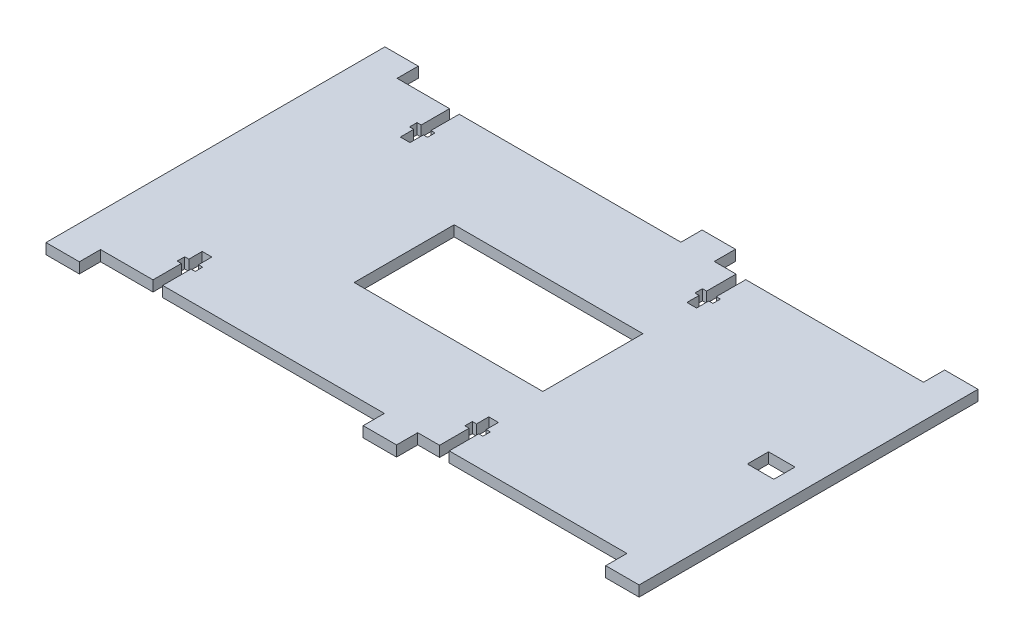
SolidWorks part; units mm, degrees
ref_plane "Front Plane" through (0, 0, 0) normal (0, 0, 1) x (1, 0, 0)
ref_plane "Top Plane" through (0, 0, 0) normal (0, 1, 0) x (1, 0, 0)
ref_plane "Right Plane" through (0, 0, 0) normal (1, 0, 0) x (0, 0, -1)
sketch "Sketch1" plane through (0, 0, 0) normal (0, 1, 0) x (1, 0, 0)
  line L0 (-67.1586, 70.4843) -> (-67.1586, 74.4928)
  line L1 (-92.8881, 91.5843) -> (-82.8881, 91.5843)
  line L2 (-92.8881, 91.5843) -> (-92.8881, -10.0157)
  line L3 (84.9141, 91.5843) -> (84.9141, -10.0157)
  line L5 (-64.2586, 85.2343) -> (2.2019, 85.2343)
  line L6 (-67.1586, 85.2343) -> (-67.1586, 76.7428)
  line L7 (-67.1586, 70.4843) -> (-64.2586, 70.4843)
  line L8 (-64.2586, 85.2343) -> (-64.2586, 76.7428)
  line L9 (-68.4086, 76.7428) -> (-67.1586, 76.7428)
  line L10 (-68.4086, 76.7428) -> (-68.4086, 74.4928)
  line L11 (-68.4086, 74.4928) -> (-67.1586, 74.4928)
  line L12 (-63.0086, 76.7428) -> (-63.0086, 74.4928)
  line L13 (18.7441, 70.4843) -> (18.7441, 74.1476)
  line L14 (-82.8881, 91.5843) -> (-82.8881, 85.2343)
  line L15 (-82.8881, 85.2343) -> (-67.1586, 85.2343)
  line L16 (2.2019, 91.5843) -> (2.2019, 85.2343)
  line L17 (-64.2586, 70.4843) -> (-64.2586, 74.4928)
  line L18 (-64.2586, 74.4928) -> (-63.0086, 74.4928)
  line L19 (-64.2586, 76.7428) -> (-63.0086, 76.7428)
  line L20 (2.2019, 91.5843) -> (12.2019, 91.5843)
  line L21 (21.6441, 85.2343) -> (74.9141, 85.2343)
  line L22 (18.7441, 85.2343) -> (18.7441, 76.3976)
  line L23 (18.7441, 70.4843) -> (21.6441, 70.4843)
  line L24 (21.6441, 85.2343) -> (21.6441, 76.3976)
  line L25 (17.4941, 76.3976) -> (18.7441, 76.3976)
  line L26 (17.4941, 76.3976) -> (17.4941, 74.1476)
  line L27 (17.4941, 74.1476) -> (18.7441, 74.1476)
  line L28 (22.8941, 76.3976) -> (22.8941, 74.1476)
  line L29 (12.2019, 91.5843) -> (12.2019, 85.2343)
  line L30 (12.2019, 85.2343) -> (18.7441, 85.2343)
  line L31 (74.9141, 91.5843) -> (74.9141, 85.2343)
  line L32 (21.6441, 70.4843) -> (21.6441, 74.1476)
  line L33 (21.6441, 74.1476) -> (22.8941, 74.1476)
  line L34 (21.6441, 76.3976) -> (22.8941, 76.3976)
  line L35 (74.9141, 91.5843) -> (84.9141, 91.5843)
  line L36 (-82.8881, -3.6657) -> (-67.1586, -3.6657)
  line L37 (74.9141, -10.0157) -> (84.9141, -10.0157)
  line L38 (21.6441, 5.171) -> (22.8941, 5.171)
  line L39 (21.6441, 7.421) -> (22.8941, 7.421)
  line L40 (21.6441, 11.0843) -> (21.6441, 7.421)
  line L41 (74.9141, -10.0157) -> (74.9141, -3.6657)
  line L42 (12.2019, -3.6657) -> (18.7441, -3.6657)
  line L43 (12.2019, -10.0157) -> (12.2019, -3.6657)
  line L44 (22.8941, 5.171) -> (22.8941, 7.421)
  line L45 (17.4941, 7.421) -> (18.7441, 7.421)
  line L46 (17.4941, 5.171) -> (17.4941, 7.421)
  line L47 (17.4941, 5.171) -> (18.7441, 5.171)
  line L48 (21.6441, -3.6657) -> (21.6441, 5.171)
  line L49 (18.7441, 11.0843) -> (21.6441, 11.0843)
  line L50 (18.7441, -3.6657) -> (18.7441, 5.171)
  line L51 (21.6441, -3.6657) -> (74.9141, -3.6657)
  line L52 (2.2019, -10.0157) -> (12.2019, -10.0157)
  line L53 (-64.2586, 4.8258) -> (-63.0086, 4.8258)
  line L54 (-64.2586, 7.0758) -> (-63.0086, 7.0758)
  line L55 (-64.2586, 11.0843) -> (-64.2586, 7.0758)
  line L56 (2.2019, -10.0157) -> (2.2019, -3.6657)
  line L57 (-82.8881, -10.0157) -> (-82.8881, -3.6657)
  line L58 (18.7441, 11.0843) -> (18.7441, 7.421)
  line L59 (-63.0086, 4.8258) -> (-63.0086, 7.0758)
  line L60 (-68.4086, 7.0758) -> (-67.1586, 7.0758)
  line L61 (-68.4086, 4.8258) -> (-68.4086, 7.0758)
  line L62 (-68.4086, 4.8258) -> (-67.1586, 4.8258)
  line L63 (-64.2586, -3.6657) -> (-64.2586, 4.8258)
  line L64 (-67.1586, 11.0843) -> (-64.2586, 11.0843)
  line L65 (-67.1586, -3.6657) -> (-67.1586, 4.8258)
  line L66 (-64.2586, -3.6657) -> (2.2019, -3.6657)
  line L67 (-92.8881, -10.0157) -> (-82.8881, -10.0157)
  line L68 (-67.1586, 11.0843) -> (-67.1586, 7.0758)
  line L69 (-36.316, 55.7843) -> (20.2598, 55.7843)
  line L70 (-36.316, 55.7843) -> (-36.316, 25.7843)
  line L71 (-36.316, 25.7843) -> (20.2598, 25.7843)
  line L72 (20.2598, 55.7843) -> (20.2598, 25.7843)
  line L75 (69.7412, 43.9593) -> (77.6787, 43.9593)
  line L76 (69.7412, 43.9593) -> (69.7412, 37.6093)
  line L77 (69.7412, 37.6093) -> (77.6787, 37.6093)
  line L78 (77.6787, 43.9593) -> (77.6787, 37.6093)
  point P76 (-36.316, 40.7843)
  point P79 (69.7412, 40.7843)
  dimension "D1" = 1.25
  dimension "D2" = 2.9
  dimension "D3" = 1.25
  dimension "D4" = 2.25
  dimension "D5" = 14.75
  dimension "D6" = 1.25
  dimension "D7" = 1.25
  dimension "D8" = 2.25
  dimension "D9" = 14.75
  dimension "D10" = 10
  dimension "D11" = 10
  dimension "D12" = 10
  dimension "D13" = 6.35
  dimension "D14" = 6.35
  dimension "D15" = 53.27
  dimension "D16" = 101.6
  dimension "D17" = 95.09
  dimension "D18" = 30
  dimension "D19" = 101.6
  dimension "D20" = 50.8
  dimension "D21" = 7.9375
  dimension "D22" = 6.35
  dimension "D23" = 50.8
  dimension "D24" = 6.35
extrude "Extrude1" add sketch "Sketch1" along normal blind 3.175 contours L59 L64 L44 L35 L31 L21 L24 L34 L28 L33 L32 L23 L13 L27 L26 L25 L22 L30 L29 L20 L16 L5 L8 L19 L12 L18 region at (-65.7086, 0, -68.4365)
